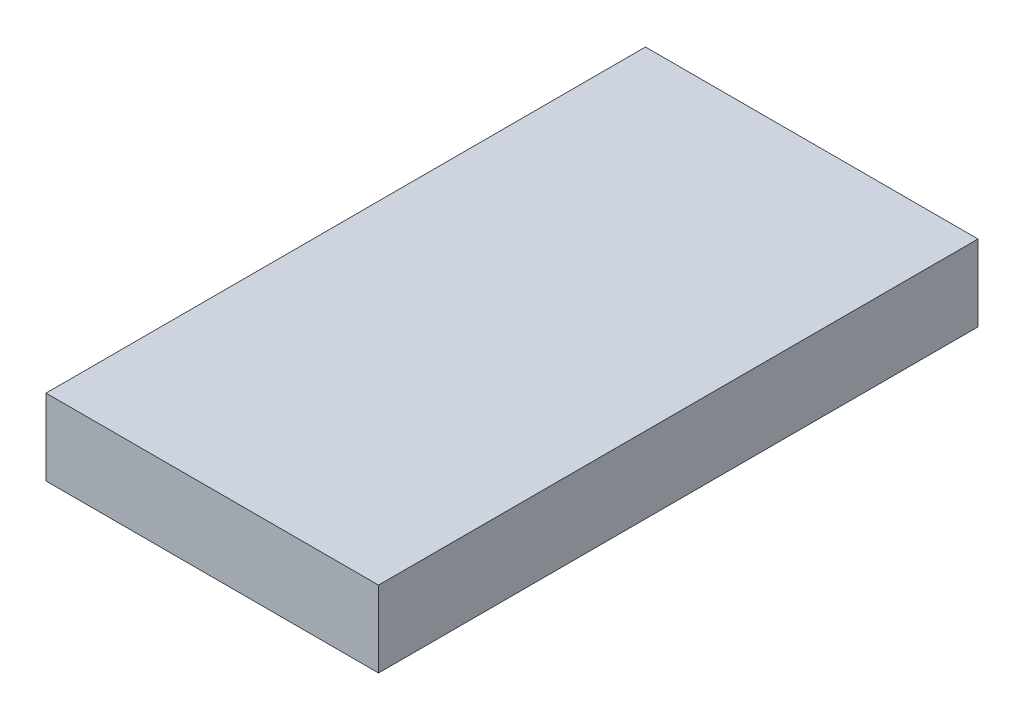
SolidWorks part; units mm, degrees
ref_plane "Front Plane" through (0, 0, 0) normal (0, 0, 1) x (1, 0, 0)
ref_plane "Top Plane" through (0, 0, 0) normal (0, 1, 0) x (1, 0, 0)
ref_plane "Right Plane" through (0, 0, 0) normal (1, 0, 0) x (0, 0, -1)
sketch "Sketch1" plane through (0, 0, 0) normal (0, 1, 0) x (1, 0, 0)
  line L1 (27.735, -50) -> (-27.735, -50)
  line L2 (27.735, -50) -> (27.735, 50)
  line L3 (27.735, 50) -> (-27.735, 50)
  line L4 (-27.735, -50) -> (-27.735, 50)
  line L5 (27.735, -50) -> (-27.735, 50) construction
  line L6 (27.735, 50) -> (-27.735, -50) construction
  point P0 (0, 0)
  dimension "D1" = 55.47
  dimension "D2" = 100
extrude "Boss-Extrude1" add sketch "Sketch1" along normal blind 12.7
ref_point "Center"
ref_plane "Qaurterway " through (0, 0, 25) normal (0, 0, 1) x (1, 0, 0)
ref_plane "Quarterway" through (0, 0, -25) normal (0, 0, 1) x (1, 0, 0)
ref_plane "Plane3" through (21.45, 0, 0) normal (1, 0, 0) x (0, 0, -1)
ref_plane "Plane4" through (-21.45, 0, 0) normal (1, 0, 0) x (0, 0, -1)
